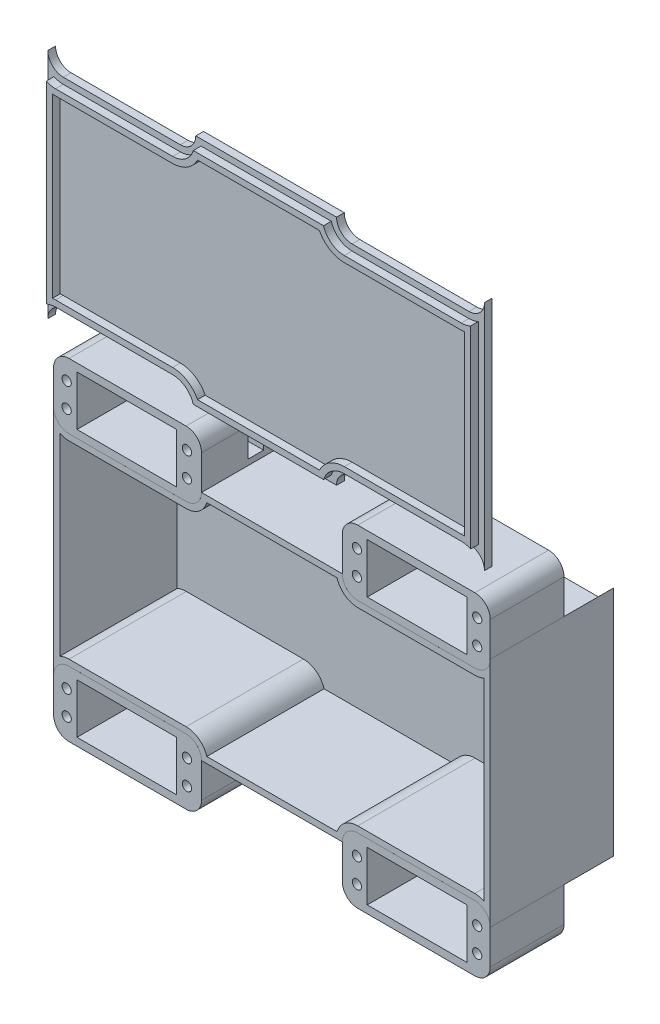
SolidWorks part; units mm, degrees
ref_plane "Front Plane" through (0, 0, 0) normal (0, 0, 1) x (1, 0, 0)
ref_plane "Top Plane" through (0, 0, 0) normal (0, 1, 0) x (1, 0, 0)
ref_plane "Right Plane" through (0, 0, 0) normal (1, 0, 0) x (0, 0, -1)
sketch "Sketch2" plane through (0, -66.8054, 0) normal (0, 0, 1) x (1, 0, 0)
  line L0 (0, 119.9477) -> (0, 114.6977) construction
  line L1 (20.5, 119.9477) -> (-20.5, 119.9477) construction
  line L2 (20.5, 119.9477) -> (20.5, 99.4477) construction
  line L3 (20.5, 99.4477) -> (-20.5, 99.4477) construction
  line L4 (-20.5, 119.9477) -> (-20.5, 99.4477) construction
  line L5 (20.5, 119.9477) -> (-20.5, 99.4477) construction
  line L6 (20.5, 99.4477) -> (-20.5, 119.9477) construction
  line L7 (-24.75, 114.6977) -> (24.75, 114.6977) construction
  line L8 (-24.75, 114.6977) -> (-24.75, 104.6977) construction
  line L9 (-24.75, 104.6977) -> (24.75, 104.6977) construction
  line L10 (24.75, 114.6977) -> (24.75, 104.6977) construction
  line L11 (-24.75, 109.6977) -> (-20.5, 109.6977) construction
  line L12 (23.7659, 123.1227) -> (-24.4, 123.1227)
  line L13 (23.7659, 96.2727) -> (-24.4, 96.2727)
  line L14 (-30.75, 116.7727) -> (-30.75, 102.6227)
  line L15 (30.1159, 102.6227) -> (30.1159, 116.7727)
  circle A0 centre (-24.75, 114.6977) radius 2.5 construction
  circle A1 centre (-24.75, 104.6977) radius 2.5 construction
  circle A2 centre (24.75, 114.6977) radius 2.5 construction
  circle A3 centre (24.75, 104.6977) radius 2.5 construction
  arc A4 (-30.75, 102.6227) -> (-24.4, 96.2727) centre (-24.4, 102.6227) ccw
  arc A5 (-24.4, 123.1227) -> (-30.75, 116.7727) centre (-24.4, 116.7727) ccw
  arc A6 (23.7659, 96.2727) -> (30.1159, 102.6227) centre (23.7659, 102.6227) ccw
  arc A7 (23.7659, 123.1227) -> (30.1159, 116.7727) centre (23.7659, 116.7727) cw
  point P0 (0, 109.6977)
  dimension "D7" = 5
  dimension "D9" = 6.35
  dimension "D1" = 20.5
  dimension "D2" = 41
  dimension "D3" = 49.5
  dimension "D4" = 10
  dimension "D5" = 3.175
  dimension "D6" = 3.175
  dimension "D8" = 6
extrude "Boss-Extrude1" add sketch "Sketch2" along normal mid plane 30.353
sketch "Sketch3" plane through (0, -66.8054, 15.1765) normal (0, 0, 1) x (1, 0, 0)
  line L0 (-20.5, 119.9477) -> (-20.5, 99.4477)
  line L1 (-20.5, 99.4477) -> (20.5, 99.4477)
  line L2 (20.5, 99.4477) -> (20.5, 119.9477)
  line L3 (20.5, 119.9477) -> (-20.5, 119.9477)
extrude "Cut-Extrude1" cut sketch "Sketch3" against normal offset from surface (27.178 mm away) 3.175 up to face at (-0.3171, 42.8923, -15.1765)
sketch "Sketch4" plane through (0, -66.8054, 15.1765) normal (0, 0, 1) x (1, 0, 0)
  circle A0 centre (-24.75, 114.6977) radius 1.905
  circle A1 centre (-24.75, 104.6977) radius 1.905
  circle A2 centre (24.75, 104.6977) radius 1.905
  circle A3 centre (24.75, 114.6977) radius 1.905
  dimension "D1" = 3.81
extrude "Cut-Extrude2" cut sketch "Sketch4" against normal blind 12.7
sketch "Sketch5" plane through (-30.75, -66.8054, 0) normal (-1, 0, 0) x (0, 0, 1)
  line L0 (-10.3505, 96.2727) -> (-10.3505, 123.1227) construction
  line L1 (-10.3505, 114.4602) -> (-4.0005, 114.4602)
  line L2 (-10.3505, 114.4602) -> (-10.3505, 104.9352)
  line L3 (-10.3505, 104.9352) -> (-4.0005, 104.9352)
  line L4 (-4.0005, 114.4602) -> (-4.0005, 104.9352)
  line L7 (15.1765, 123.1227) -> (-15.1765, 123.1227) construction
  line L8 (15.1765, 96.2727) -> (-15.1765, 96.2727) construction
  line L9 (-15.1765, 116.7727) -> (-15.1765, 102.6227) construction
  point P9 (-10.3505, 109.6977)
  dimension "D1" = 9.525
  dimension "D2" = 6.35
  dimension "D3" = 4.826
extrude "Cut-Extrude3" cut sketch "Sketch5" against normal up to surface (10.25 mm away) up to face at (-20.5, 42.8923, 1.5875)
sketch "Sketch7" plane through (0, -66.8054, 15.1765) normal (0, 0, 1) x (1, 0, 0)
  line L0 (-59.7203, 102.6213) -> (-59.7203, 7.075)
  line L1 (-30.75, 7.075) -> (-149.5565, 7.075)
  line L2 (30.1159, 7.075) -> (30.1159, 102.6213)
  line L5 (-30.75, 102.6213) -> (-88.6906, 102.6213)
  line L11 (-149.5565, 7.075) -> (-149.5565, 102.6213)
  line L16 (23.7659, 13.425) -> (-24.4, 13.425)
  line L22 (23.7659, -13.425) -> (-24.4, -13.425)
  line L27 (23.7659, 123.1213) -> (-24.4, 123.1213)
  line L28 (23.7659, 96.2713) -> (-24.4, 96.2713)
  line L31 (-30.75, 116.7713) -> (-30.75, 102.6213)
  line L33 (30.1159, 102.6213) -> (30.1159, 116.7713)
  line L38 (-30.75, 7.075) -> (-30.75, -7.075)
  line L43 (-95.0406, 123.1213) -> (-143.2065, 123.1213)
  line L45 (-95.0406, 96.2713) -> (-143.2065, 96.2713)
  line L46 (-149.5565, 116.7713) -> (-149.5565, 102.6213)
  line L49 (-88.6906, 102.6213) -> (-88.6906, 116.7713)
  line L54 (30.1159, -7.075) -> (30.1159, 7.075)
  line L71 (-95.0406, 13.425) -> (-143.2065, 13.425)
  line L72 (-95.0406, -13.425) -> (-143.2065, -13.425)
  line L73 (-149.5565, 7.075) -> (-149.5565, -7.075)
  line L74 (-88.6906, -7.075) -> (-88.6906, 7.075)
  arc A28 (-149.5565, -7.075) -> (-143.2065, -13.425) centre (-143.2065, -7.075) ccw
  arc A29 (-143.2065, 13.425) -> (-149.5565, 7.075) centre (-143.2065, 7.075) ccw
  arc A30 (-95.0406, -13.425) -> (-88.6906, -7.075) centre (-95.0406, -7.075) ccw
  arc A31 (-95.0406, 13.425) -> (-88.6906, 7.075) centre (-95.0406, 7.075) cw
  arc A32 (-149.5565, 102.6213) -> (-143.2065, 96.2713) centre (-143.2065, 102.6213) ccw
  arc A33 (-143.2065, 123.1213) -> (-149.5565, 116.7713) centre (-143.2065, 116.7713) ccw
  arc A34 (-95.0406, 96.2713) -> (-88.6906, 102.6213) centre (-95.0406, 102.6213) ccw
  arc A35 (-95.0406, 123.1213) -> (-88.6906, 116.7713) centre (-95.0406, 116.7713) cw
  arc A36 (-30.75, 102.6213) -> (-24.4, 96.2713) centre (-24.4, 102.6213) ccw
  arc A37 (-24.4, 123.1213) -> (-30.75, 116.7713) centre (-24.4, 116.7713) ccw
  arc A38 (23.7659, 96.2713) -> (30.1159, 102.6213) centre (23.7659, 102.6213) ccw
  arc A39 (23.7659, 123.1213) -> (30.1159, 116.7713) centre (23.7659, 116.7713) cw
  arc A40 (-30.75, -7.075) -> (-24.4, -13.425) centre (-24.4, -7.075) ccw
  arc A41 (-24.4, 13.425) -> (-30.75, 7.075) centre (-24.4, 7.075) ccw
  arc A42 (23.7659, -13.425) -> (30.1159, -7.075) centre (23.7659, -7.075) ccw
  arc A43 (23.7659, 13.425) -> (30.1159, 7.075) centre (23.7659, 7.075) cw
  point P4 (0, 0)
  point P19 (0, 0)
  point P20 (30.7421, 7.075)
  point P121 (-88.6906, 0)
  dimension "D3" = 6.35
  dimension "D6" = 6.35
  dimension "D9" = 6.35
  dimension "D12" = 6.35
  dimension "D1" = 26.85
  dimension "D2" = 60.8659
  dimension "D4" = 60.8659
  dimension "D5" = 26.85
  dimension "D7" = 60.8659
  dimension "D8" = 26.85
  dimension "D10" = 26.85
  dimension "D11" = 60.8659
extrude "Boss-Extrude2" add sketch "Sketch7" against normal blind 50.8 separate body contours L16 A43 L2 A38 L28 A36 L5 L0 L1 A41 | A34 L45 A32 L11 A29 L71 A31 L1 L0 L5 region at (-16.1656, -11.9572, 15.1765) region at (-103.2751, -11.9572, 15.1765)
sketch "Sketch10" plane through (0, 0, 15.1765) normal (0, 0, 1) x (1, 0, 0)
  line L0 (30.1159, -11.9572) -> (-149.5565, -11.9572)
  line L1 (30.1159, -59.7304) -> (30.1159, 35.8159) construction
  line L2 (-149.5565, -59.7304) -> (-149.5565, 35.8159) construction
  line L3 (-59.7203, -11.9572) -> (-59.7203, 45.542)
  line L4 (-59.7203, 45.542) -> (-59.7203, -104.1349)
ref_plane "Plane1" through (0, -11.9572, 0) normal (0, -1, 0) x (1, 0, 0)
mirror "Mirror1" about plane through (0, -11.9572, 0) normal (0, -1, 0) of bodies 104
ref_plane "Plane2" through (-59.7203, 0, 0) normal (-1, 0, 0) x (0, -1, 0)
mirror "Mirror2" about plane through (-59.7203, 0, 0) normal (-1, 0, 0) of bodies 104 112
sketch "Sketch11" plane through (0, 0, 15.1765) normal (0, 0, 1) x (1, 0, 0)
  line L4 (-138.431, 27.8982) -> (-138.431, 29.4673)
  line L5 (-95.0406, 29.4673) -> (-143.2065, 29.4673) construction
  line L6 (-137.672, -52.1118) -> (-137.672, -53.3818)
  line L7 (-95.0406, -53.3818) -> (-143.2065, -53.3818) construction
  dimension "D2" = 1.27
shell "Shell2" thickness 2.54 removed face at (-59.7203, -11.9572, 15.1765)
sketch "Sketch15" plane through (209.6584, 80.9526, 15.1765) normal (0, 0, 1) x (1, 0, 0)
  line L1 (-239.6097, -11.6122) -> (-297.5504, -11.6122)
  line L2 (-178.7438, -11.6122) -> (-178.7438, 83.9341)
  line L3 (-239.6097, 83.9341) -> (-297.5504, 83.9341)
  line L4 (-358.4162, -11.6122) -> (-358.4162, 83.9341)
  line L5 (-185.0938, -5.2622) -> (-233.2597, -5.2622)
  line L8 (-185.0938, 77.5841) -> (-233.2597, 77.5841)
  line L13 (-303.9004, 77.5841) -> (-352.0662, 77.5841)
  line L17 (-303.9004, -5.2622) -> (-352.0662, -5.2622)
  arc A1 (-352.0662, -5.2622) -> (-358.4162, -11.6122) centre (-352.0662, -11.6122) ccw
  arc A3 (-303.9004, -5.2622) -> (-297.5504, -11.6122) centre (-303.9004, -11.6122) cw
  arc A4 (-358.4162, 83.9341) -> (-352.0662, 77.5841) centre (-352.0662, 83.9341) ccw
  arc A6 (-303.9004, 77.5841) -> (-297.5504, 83.9341) centre (-303.9004, 83.9341) ccw
  arc A8 (-239.6097, 83.9341) -> (-233.2597, 77.5841) centre (-233.2597, 83.9341) ccw
  arc A10 (-185.0938, 77.5841) -> (-178.7438, 83.9341) centre (-185.0938, 83.9341) ccw
  arc A13 (-233.2597, -5.2622) -> (-239.6097, -11.6122) centre (-233.2597, -11.6122) ccw
  arc A15 (-185.0938, -5.2622) -> (-178.7438, -11.6122) centre (-185.0938, -11.6122) cw
  point P51 (0, 0)
  dimension "D3" = 6.35
  dimension "D12" = 6.35
extrude "Boss-Extrude3" add sketch "Sketch15" along normal blind 3.175 separate body
sketch "Sketch16" plane through (0, 0, 18.3515) normal (0, 0, 1) x (1, 0, 0)
  line L0 (28.3775, 77.3621) -> (28.3775, 156.844)
  line L6 (24.5675, 78.2199) -> (-23.5984, 78.2199)
  line L7 (-32.1178, 71.8699) -> (-85.7196, 71.8699)
  line L9 (-94.239, 78.2199) -> (-142.4049, 78.2199)
  line L10 (-146.2149, 77.3621) -> (-146.2149, 156.844)
  line L11 (-94.239, 155.9861) -> (-142.4049, 155.9861)
  line L12 (-32.1178, 162.3361) -> (-85.7196, 162.3361)
  line L14 (24.5675, 155.9861) -> (-23.5984, 155.9861)
  line L15 (25.8375, 80.6891) -> (25.8375, 153.5169)
  line L16 (24.5675, 80.7599) -> (-23.5984, 80.7599)
  line L17 (-33.8375, 74.4099) -> (-84, 74.4099)
  line L18 (-94.239, 80.7599) -> (-142.4049, 80.7599)
  line L19 (-143.6749, 80.6891) -> (-143.6749, 153.5169)
  line L20 (-94.239, 153.4461) -> (-142.4049, 153.4461)
  line L21 (-33.8375, 159.7961) -> (-84, 159.7961)
  line L22 (24.5675, 153.4461) -> (-23.5984, 153.4461)
  arc A5 (24.5675, 155.9861) -> (28.3775, 156.844) centre (24.5675, 164.8761) ccw
  arc A7 (24.5675, 78.2199) -> (28.3775, 77.3621) centre (24.5675, 69.3299) cw
  arc A9 (-23.5984, 78.2199) -> (-32.1178, 71.8699) centre (-23.5984, 69.3299) ccw
  arc A11 (-94.239, 78.2199) -> (-85.7196, 71.8699) centre (-94.239, 69.3299) cw
  arc A12 (-142.4049, 78.2199) -> (-146.2149, 77.3621) centre (-142.4049, 69.3299) ccw
  arc A14 (-146.2149, 156.844) -> (-142.4049, 155.9861) centre (-142.4049, 164.8761) ccw
  arc A16 (-94.239, 155.9861) -> (-85.7196, 162.3361) centre (-94.239, 164.8761) ccw
  arc A17 (-32.1178, 162.3361) -> (-23.5984, 155.9861) centre (-23.5984, 164.8761) ccw
  arc A18 (24.5675, 153.4461) -> (25.8375, 153.5169) centre (24.5675, 164.8761) ccw
  arc A19 (24.5675, 80.7599) -> (25.8375, 80.6891) centre (24.5675, 69.3299) cw
  arc A20 (-23.5984, 80.7599) -> (-33.8375, 74.4099) centre (-23.5984, 69.3299) ccw
  arc A21 (-94.239, 80.7599) -> (-84, 74.4099) centre (-94.239, 69.3299) cw
  arc A22 (-142.4049, 80.7599) -> (-143.6749, 80.6891) centre (-142.4049, 69.3299) ccw
  arc A23 (-143.6749, 153.5169) -> (-142.4049, 153.4461) centre (-142.4049, 164.8761) ccw
  arc A24 (-94.239, 153.4461) -> (-84, 159.7961) centre (-94.239, 164.8761) ccw
  arc A25 (-33.8375, 159.7961) -> (-23.5984, 153.4461) centre (-23.5984, 164.8761) ccw
  point P4 (0, 0)
  point P5 (0, 0)
  dimension "D1" = 2.54
extrude "Boss-Extrude4" add sketch "Sketch16" along normal blind 3.175
